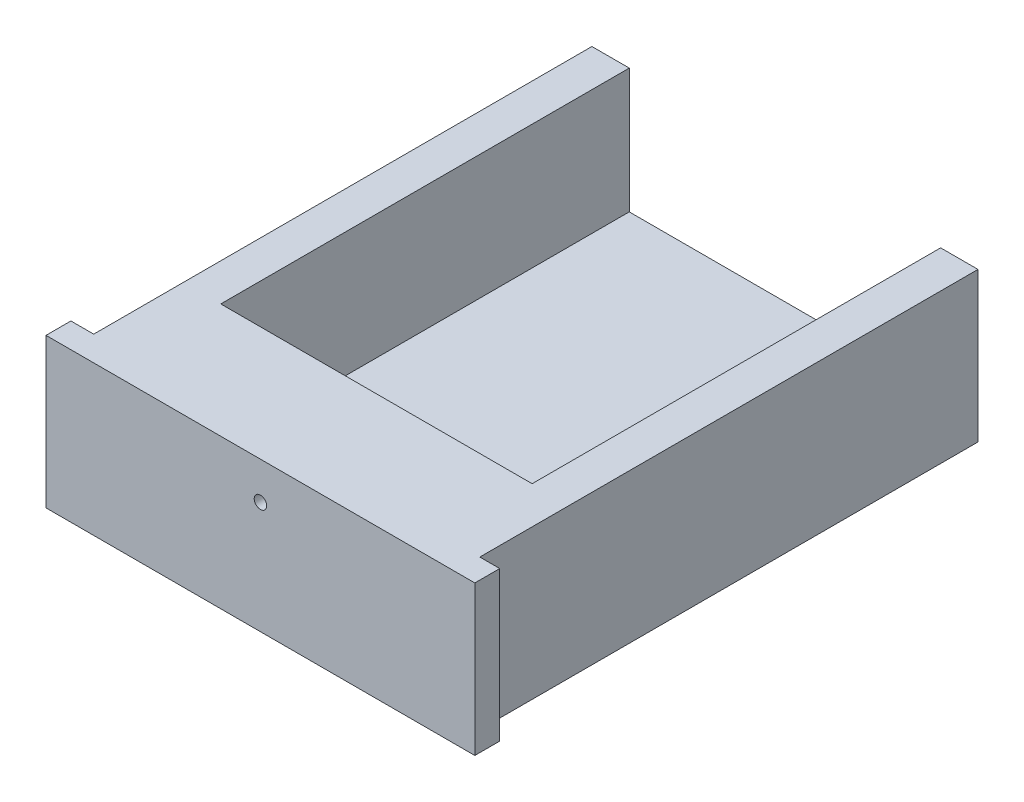
SolidWorks part; units mm, degrees
ref_plane "Front Plane" through (0, 0, 0) normal (0, 0, 1) x (1, 0, 0)
ref_plane "Top Plane" through (0, 0, 0) normal (0, 1, 0) x (1, 0, 0)
ref_plane "Right Plane" through (0, 0, 0) normal (1, 0, 0) x (0, 0, -1)
sketch "Sketch3" plane through (0, 0.0003, -31.967) normal (0, 0, 1) x (1, 0, 0)
  line L0 (106.7306, 145.4577) -> (106.7306, 86.6568) construction
  line L3 (98.9806, 85.6568) -> (114.4806, 85.6568)
  line L5 (98.9806, 145.4576) -> (98.9806, 71.6476) construction
  line L6 (100.4806, 86.6568) -> (112.9806, 86.6568)
  line L7 (114.4806, 145.4575) -> (114.4806, 71.6475) construction
  line L10 (98.9806, 85.6568) -> (98.9806, 91.6568)
  line L11 (98.9806, 91.6568) -> (100.4806, 91.6568)
  line L12 (100.4806, 86.6568) -> (100.4806, 91.6568)
  line L14 (114.4806, 85.6568) -> (114.4806, 91.6568)
  line L15 (114.4806, 91.6568) -> (112.9806, 91.6568)
  line L16 (112.9806, 86.6568) -> (112.9806, 91.6568)
  dimension "D3" = 1
  dimension "D5" = 1.5
  dimension "D6" = 5
extrude "Boss-Extrude1" add sketch "Sketch3" along normal up to surface (20 mm away)
sketch "Sketch4" plane through (0, 0.0001, -11.967) normal (0, 0, 1) x (1, 0, 0)
  line L0 (114.4806, 91.6568) -> (116.0806, 91.6568) construction
  line L1 (98.0647, 91.6568) -> (115.2806, 91.6568)
  line L2 (98.0647, 91.6568) -> (98.0647, 85.6568)
  line L3 (98.0647, 85.6568) -> (115.2806, 85.6568)
  line L4 (115.2806, 91.6568) -> (115.2806, 85.6568)
  line L8 (114.4806, 145.4575) -> (114.4806, 71.6475) construction
  line L14 (116.0806, 145.4575) -> (116.0806, 71.6475) construction
  line L15 (97.3806, 91.6568) -> (98.9806, 91.6568) construction
  line L16 (114.4806, 85.6568) -> (98.9806, 85.6568) construction
  line L17 (97.3806, 145.4576) -> (97.3806, 71.6476) construction
  line L18 (98.9806, 145.4576) -> (98.9806, 71.6476) construction
  line L22 (98.9806, 91.6568) -> (100.4806, 91.6568) construction
extrude "Boss-Extrude2" add sketch "Sketch4" along normal blind 1
sketch "Sketch6" plane through (0, 0.0001, -10.967) normal (0, 0, 1) x (1, 0, 0)
  line L0 (98.0647, 88.6568) -> (115.2806, 88.6568) construction
  line L1 (98.0647, 91.6568) -> (98.0647, 85.6568) construction
  line L2 (115.2806, 85.6568) -> (115.2806, 91.6568) construction
  line L3 (106.6727, 91.6568) -> (106.6727, 85.6568) construction
  line L4 (115.2806, 91.6568) -> (98.0647, 91.6568) construction
  line L5 (98.0647, 85.6568) -> (115.2806, 85.6568) construction
  line L6 (98.0647, 90.1568) -> (115.2806, 90.1568) construction
  line L7 (98.0647, 91.6568) -> (98.0647, 85.6568) construction
  line L8 (115.2806, 85.6568) -> (115.2806, 91.6568) construction
  dimension "D1" = 1.5
sketch "Sketch7" plane through (0, 0.0001, -11.967) normal (0, 0, -1) x (-1, 0, 0)
  line L4 (-112.9806, 91.6568) -> (-112.9806, 86.6568)
  line L5 (-112.9806, 86.6568) -> (-100.4806, 86.6568)
  line L6 (-100.4806, 86.6568) -> (-100.4806, 91.6568)
  line L7 (-100.4806, 91.6568) -> (-112.9806, 91.6568)
  line L8 (-112.9806, 91.6568) -> (-112.9806, 86.6568)
  line L9 (-112.9806, 86.6568) -> (-100.4806, 86.6568)
  line L10 (-100.4806, 86.6568) -> (-100.4806, 91.6568)
  line L11 (-100.4806, 91.6568) -> (-112.9806, 91.6568)
  dimension "D1" = 0
extrude "Boss-Extrude3" add sketch "Sketch7" along normal blind 3.6
sketch "Sketch8" plane through (0, 0.0001, -10.967) normal (0, 0, 1) x (1, 0, 0)
  line L0 (98.0647, 90.1568) -> (115.2806, 90.1568) construction
  point P0 (106.6727, 90.1568)
hole_wizard "Ø1.0mm Dowel Hole1" positions "Sketch10" profile "Sketch11" hole size "Ø1.0" standard "AS" end condition up to next
sketch "Sketch10" plane through (0, 0.0001, -10.967) normal (0, 0, 1) x (1, 0, 0)
  point P0 (106.6727, 90.1568)
sketch "Sketch11" plane through (106.6727, 90.1569, -10.9663) normal (1, 0, 0) x (0, -1, 0)
  line L0 (0, 0) -> (0, 4.6)
  line L1 (0, 4.6) -> (0.25, 4.6)
  line L2 (0.25, 4.6) -> (0.25, 0)
  line L5 (0.25, 0) -> (0, 0)
  line L11 (0, -6.35) -> (0, 107.95) construction
  dimension "Thru Hole Dia." = 0.5
  dimension "Thru Hole Depth" = 4.6
